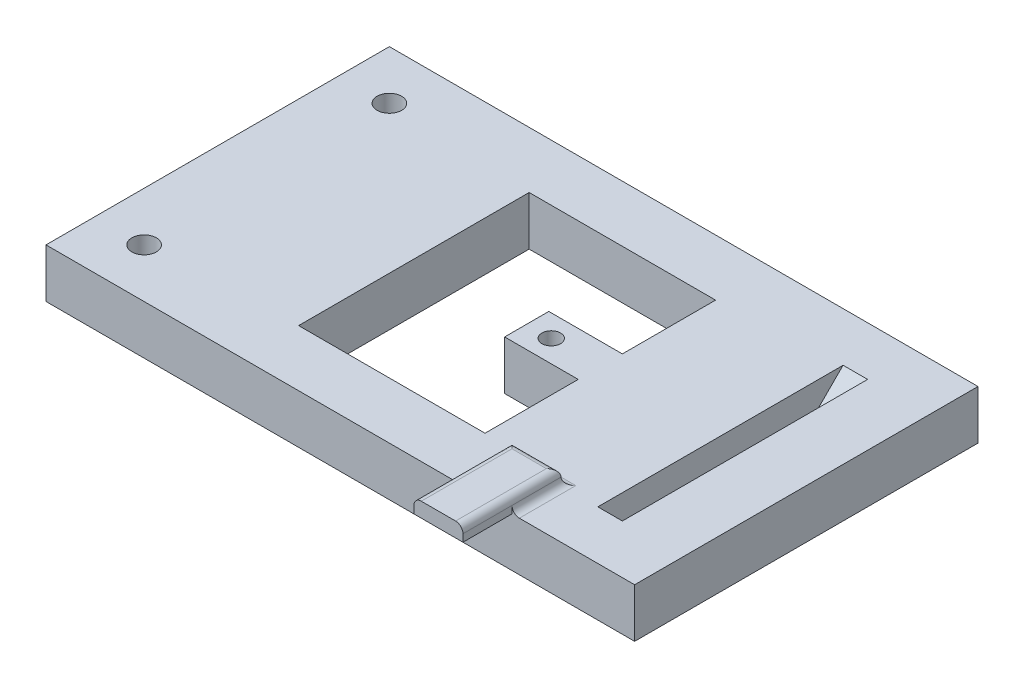
SolidWorks part; units mm, degrees
ref_plane "Front Plane" through (0, 0, 0) normal (0, 0, 1) x (1, 0, 0)
ref_plane "Top Plane" through (0, 0, 0) normal (0, 1, 0) x (1, 0, 0)
ref_plane "Right Plane" through (0, 0, 0) normal (1, 0, 0) x (0, 0, -1)
sketch "Sketch1" plane through (0, 0, 0) normal (0, 1, 0) x (1, 0, 0)
  line L0 (-60, 0) -> (60, 0) construction
  line L1 (-60, -35) -> (60, -35)
  line L2 (-60, -35) -> (-60, 35)
  line L3 (-60, 35) -> (60, 35)
  line L4 (60, -35) -> (60, 35)
  line L5 (-60, -35) -> (60, 35) construction
  line L6 (-60, 35) -> (60, -35) construction
  line L7 (18, 23.5) -> (18, 4.5)
  line L8 (-20, -23.5) -> (18, -23.5)
  line L9 (-20, -23.5) -> (-20, 23.5)
  line L10 (-20, 23.5) -> (18, 23.5)
  line L11 (18, -23.5) -> (18, 23.5) construction
  line L12 (-20, -23.5) -> (18, 23.5) construction
  line L13 (-20, 23.5) -> (18, -23.5) construction
  line L14 (42.5, -15) -> (47.5, -15)
  line L15 (42.5, -15) -> (42.5, 15)
  line L16 (42.5, 15) -> (47.5, 15)
  line L17 (47.5, -15) -> (47.5, 15)
  line L18 (42.5, -15) -> (47.5, 15) construction
  line L19 (42.5, 15) -> (47.5, -15) construction
  line L20 (18, 4.5) -> (3, 4.5)
  line L21 (3, 4.5) -> (3, -4.5)
  line L22 (3, -4.5) -> (18, -4.5)
  line L23 (18, -4.5) -> (18, -23.5)
  circle A0 centre (-50, 25) radius 2.5
  circle A1 centre (-50, -25) radius 2.5
  circle A2 centre (8, 0) radius 1.9
  point P0 (0, 0)
  point P12 (-1, 0)
  point P17 (45, 0)
  point P26 (3, 0)
  dimension "D3" = 5
  dimension "D13" = 3.8
  dimension "D1" = 70
  dimension "D2" = 120
  dimension "D4" = 10
  dimension "D5" = 10
  dimension "D6" = 38
  dimension "D7" = 47
  dimension "D8" = 5
  dimension "40" = 40
  dimension "D9" = 30
  dimension "D10" = 15
  dimension "D11" = 9
  dimension "D12" = 15
  dimension "D14" = 5
extrude "Boss-Extrude1" add sketch "Sketch1" along normal blind 10
chamfer "Chamfer1" distance 10 angle 45 2 edges at (45, 10, 15) (45, 10, -15)
sketch "Sketch3" plane through (0, 10, 0) normal (0, 1, 0) x (1, 0, 0)
  line L0 (-60, -35) -> (60, -35) construction
  line L1 (25, -45) -> (35, -45)
  line L2 (25, -45) -> (25, -25)
  line L3 (25, -25) -> (35, -25)
  line L4 (35, -45) -> (35, -25)
  line L5 (25, -45) -> (35, -25) construction
  line L6 (25, -25) -> (35, -45) construction
  line L7 (60, -35) -> (60, 35) construction
  point P0 (30, -35)
  dimension "D1" = 10
  dimension "D2" = 20
  dimension "D3" = 30
extrude "Boss-Extrude2" add sketch "Sketch3" along normal blind 3
fillet "Fillet1" radius 1.5 6 edges at (25, 13, 35) (35, 13, 35) (30, 13, 25) (35, 10, 30) (30, 10, 25) (25, 10, 30)
